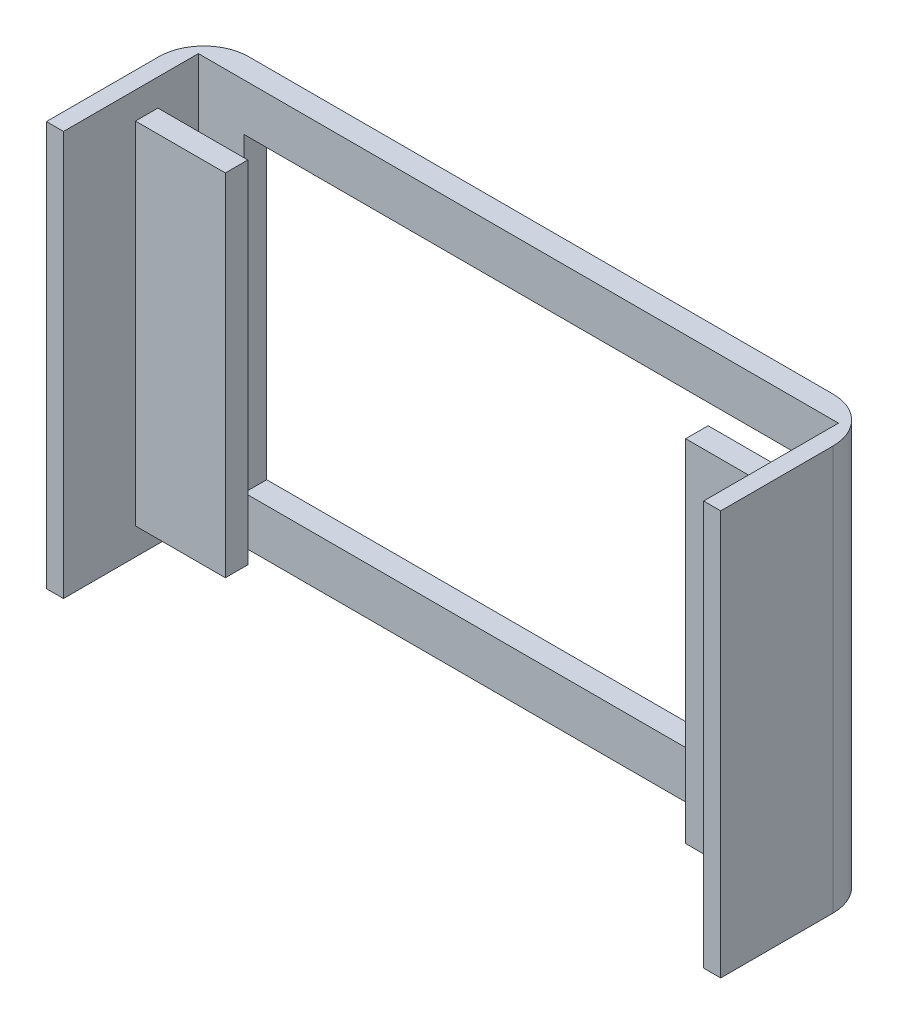
SolidWorks part; units mm, degrees
ref_plane "Front Plane" through (0, 0, 0) normal (0, 0, 1) x (1, 0, 0)
ref_plane "Top Plane" through (0, 0, 0) normal (0, 1, 0) x (1, 0, 0)
ref_plane "Right Plane" through (0, 0, 0) normal (1, 0, 0) x (0, 0, -1)
sketch "Sketch1" plane through (0, 0, 0) normal (0, 0, 1) x (1, 0, 0)
  line L1 (-75, 45) -> (75, 45)
  line L2 (-75, 45) -> (-75, -45)
  line L3 (-75, -45) -> (75, -45)
  line L4 (75, 45) -> (75, -45)
  line L5 (-75, 45) -> (75, -45) construction
  line L6 (-75, -45) -> (75, 45) construction
  line L7 (-61, 34.5) -> (61, 34.5)
  line L8 (-61, 34.5) -> (-61, -34.5)
  line L9 (-61, -34.5) -> (61, -34.5)
  line L10 (61, 34.5) -> (61, -34.5)
  line L11 (-61, 34.5) -> (61, -34.5) construction
  line L12 (-61, -34.5) -> (61, 34.5) construction
  point P0 (0, 0)
  point P6 (0, 0)
  dimension "D1" = 122
  dimension "D2" = 150
  dimension "D3" = 69
  dimension "D4" = 90
extrude "Boss-Extrude1" add sketch "Sketch1" along normal blind 5
sketch "Sketch2" plane through (0, 0, 5) normal (0, 0, 1) x (1, 0, 0)
  line L0 (-75, -45) -> (75, -45) construction
  line L1 (-75, 45) -> (-71.2, 45)
  line L2 (-75, 45) -> (-75, -45)
  line L3 (-75, -45) -> (-71.2, -45)
  line L4 (-71.2, 45) -> (-71.2, -45)
  line L5 (0, 0) -> (0, 45) construction
  line L6 (75, 45) -> (-75, 45) construction
  line L7 (75, -45) -> (71.2, -45)
  line L8 (71.2, 45) -> (71.2, -45)
  line L9 (75, 45) -> (71.2, 45)
  line L10 (75, 45) -> (75, -45)
  dimension "D1" = 3.8
extrude "Boss-Extrude2" add sketch "Sketch2" along normal blind 30
fillet "Fillet1" radius 10 2 edges at (-75, 0, 0) (75, 0, 0)
sketch "Sketch3" plane through (0, 45, 0) normal (0, 1, 0) x (1, 0, 0)
  line L0 (-71.2, -35) -> (-71.2, -5) construction
  line L1 (-71.2, -14) -> (-51.2, -14)
  line L2 (-71.2, -14) -> (-71.2, -19)
  line L3 (-71.2, -19) -> (-51.2, -19)
  line L4 (-51.2, -14) -> (-51.2, -19)
  line L5 (71.2, -35) -> (71.2, -5) construction
  line L6 (71.2, -14) -> (51.2, -14)
  line L7 (71.2, -14) -> (71.2, -19)
  line L8 (71.2, -19) -> (51.2, -19)
  line L9 (51.2, -14) -> (51.2, -19)
  line L10 (71.2, -5) -> (-71.2, -5) construction
  dimension "D1" = 9
  dimension "D2" = 9
  dimension "D3" = 5
  dimension "D4" = 5
  dimension "D5" = 20
  dimension "D6" = 20
extrude "Boss-Extrude3" add sketch "Sketch3" against normal up to surface (90 mm away) up to face at (0, -45, 16.5858)
sketch "Sketch4" plane through (0, 0, 19) normal (0, 0, 1) x (1, 0, 0)
  line L0 (71.2, -45) -> (71.2, 45) construction
  line L1 (-71.2, 45) -> (71.2, 45)
  line L2 (-71.2, 45) -> (-71.2, 39)
  line L3 (-71.2, 39) -> (71.2, 39)
  line L4 (71.2, 45) -> (71.2, 39)
  line L5 (0, 0) -> (-71.2, 0) construction
  line L6 (-71.2, -45) -> (-71.2, 45) construction
  line L7 (-71.2, -39) -> (71.2, -39)
  line L8 (71.2, -45) -> (71.2, -39)
  line L9 (-71.2, -45) -> (71.2, -45)
  line L10 (-71.2, -45) -> (-71.2, -39)
  dimension "D1" = 6
extrude "Cut-Extrude1" cut sketch "Sketch4" against normal blind 5
